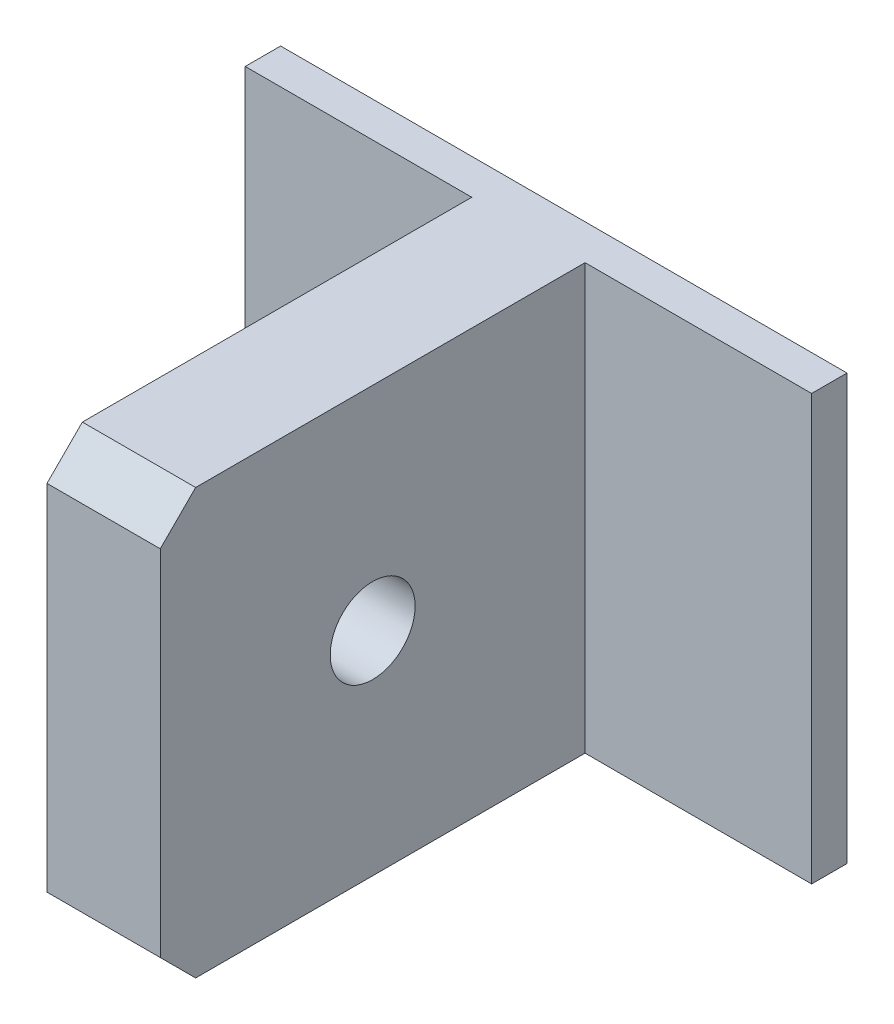
SolidWorks part; units mm, degrees
material "AISI 1020"
ref_plane "Alzado" through (0, 0, 0) normal (0, 0, 1) x (1, 0, 0)
ref_plane "Planta" through (0, 0, 0) normal (0, 1, 0) x (1, 0, 0)
ref_plane "Vista lateral" through (0, 0, 0) normal (1, 0, 0) x (0, 0, -1)
sketch "Croquis3" plane through (0, 0, 0) normal (0, 0, 1) x (1, 0, 0)
  line L1 (-40, -30) -> (40, -30)
  line L2 (-40, -30) -> (-40, 30)
  line L3 (-40, 30) -> (40, 30)
  line L4 (40, -30) -> (40, 30)
  line L9 (-8, 30) -> (8, 30)
  line L10 (-8, 30) -> (-8, -30)
  line L11 (-8, -30) -> (8, -30)
  line L12 (8, 30) -> (8, -30)
  point P6 (0, -30)
  point P7 (0, 30)
  point P8 (-40, 0)
  point P9 (40, 0)
  point P13 (0, -30)
  point P14 (0, 30)
  dimension "D1" = 80
  dimension "D2" = 60
  dimension "D3" = 16
extrude "Saliente-Extruir1" add sketch "Croquis3" against normal blind 5 contours L4 L3 L2 L1
extrude "Saliente-Extruir2" add sketch "Croquis3<4>" along normal blind 60 contours L12 L3 L10 L1 region at (0, 0, 0)
sketch "Croquis3<4>" plane through (0, 0, 0) normal (0, 0, 1) x (1, 0, 0) same geometry as "Croquis3"
fillet "Chaflán1" radius 5 1 edges at (0, 30, 60) type face fillet profile chamfer first side face at (0, 30, 13.75) second side face at (0, 0, 60)
sketch "Croquis4" plane through (8, 0, 0) normal (1, 0, 0) x (0, 0, -1)
  line L0 (0, 30) -> (0, -30) construction
  line L1 (-60, -30) -> (0, -30) construction
  circle A0 centre (-30, 0) radius 6
  dimension "D1" = 12
  dimension "D2" = 30
  dimension "D3" = 30
extrude "Cortar-Extruir1" cut sketch "Croquis4" against normal blind 60
fillet "Chaflán2" radius 5 1 edges at (0, -30, 60) type face fillet profile chamfer first side face at (0, -2.5, 60) second side face at (0, -30, 13.75)
